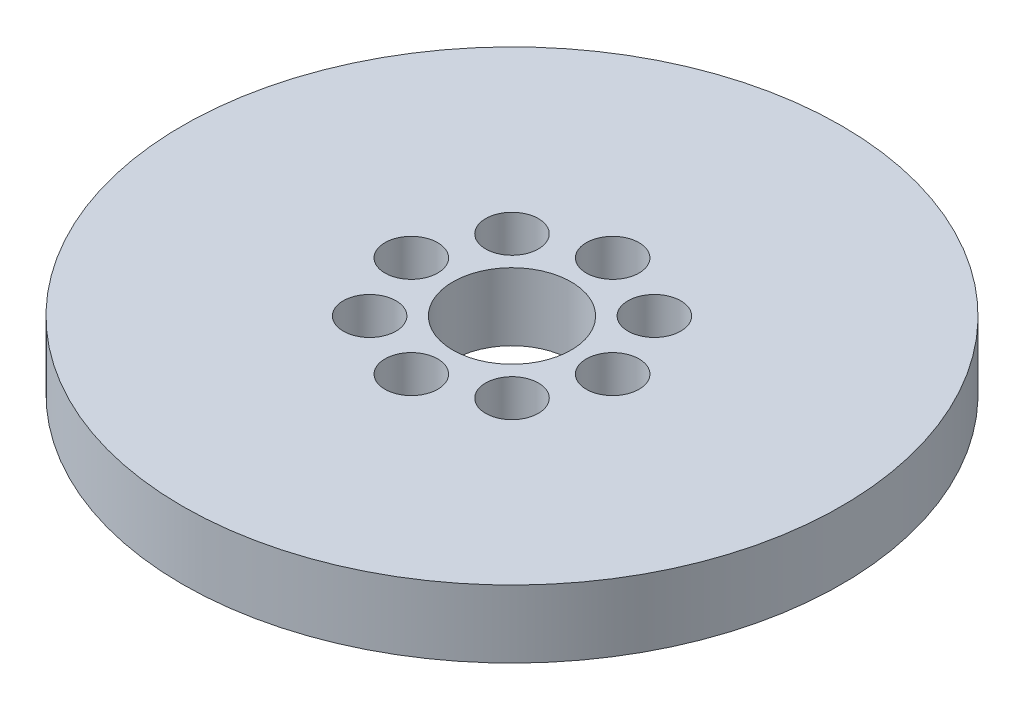
SolidWorks part; units mm, degrees
ref_plane "Front Plane" through (0, 0, 0) normal (0, 0, 1) x (1, 0, 0)
ref_plane "Top Plane" through (0, 0, 0) normal (0, 1, 0) x (1, 0, 0)
ref_plane "Right Plane" through (0, 0, 0) normal (1, 0, 0) x (0, 0, -1)
sketch "Sketch1" plane through (0, 0, 0) normal (0, 1, 0) x (1, 0, 0)
  circle A0 centre (0, 0) radius 97.5
  dimension "FLANGE_OD" = 195
extrude "Boss-Extrude1" add sketch "Sketch1" along normal blind 20
sketch "Sketch2" plane through (0, 0, 0) normal (0, 1, 0) x (1, 0, 0)
  circle A0 centre (0, 0) radius 17.5
  dimension "BORE_D" = 35
extrude "Cut-Extrude1" cut sketch "Sketch2" along normal through all
sketch "Sketch3" plane through (0, 20, 0) normal (0, 1, 0) x (1, 0, 0)
  circle A0 centre (0, 0) radius 29.784 construction
  circle A1 centre (-29.784, 0) radius 7.8022
  dimension "BOLT_D" = 15.6045
  dimension "BOLT_PCD" = 59.5679
extrude "Cut-Extrude2" cut sketch "Sketch3" against normal blind 15.6588
pattern_circular "CirPattern1" count 8 over 360 about axis through (0, 0, 0) along (0, 1, 0) of "Cut-Extrude2"
